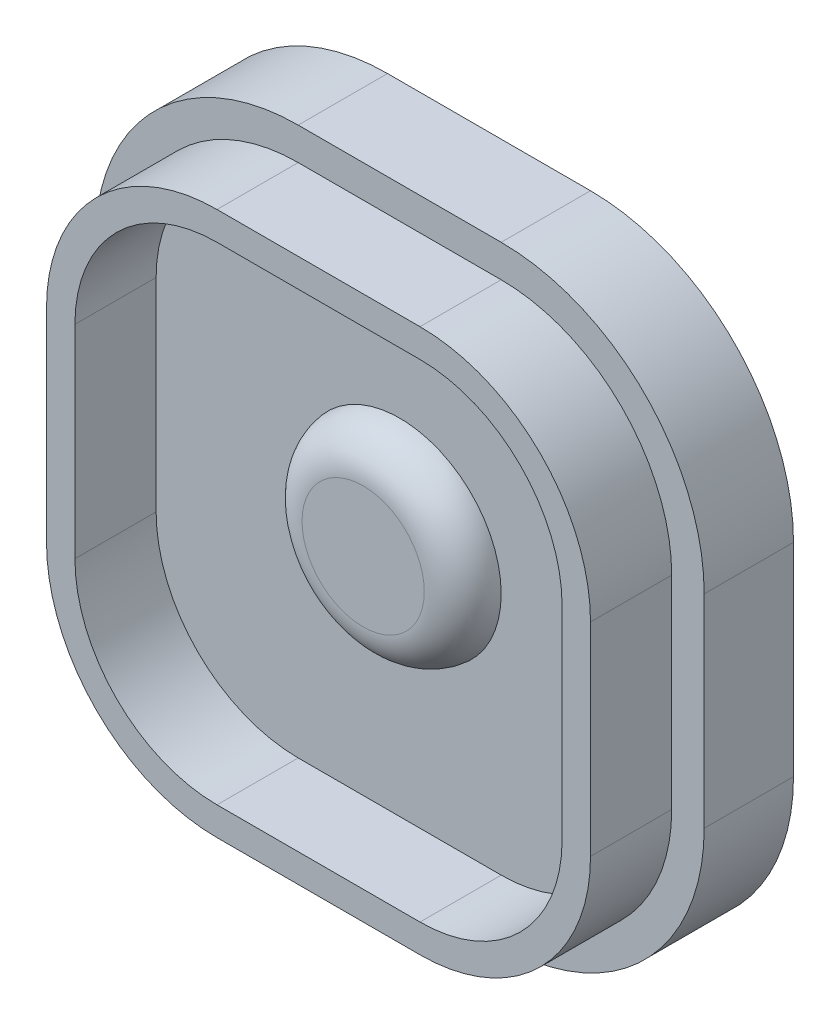
SolidWorks part; units mm, degrees
ref_plane "Front Plane" through (0, 0, 0) normal (0, 0, 1) x (1, 0, 0)
ref_plane "Top Plane" through (0, 0, 0) normal (0, 1, 0) x (1, 0, 0)
ref_plane "Right Plane" through (0, 0, 0) normal (1, 0, 0) x (0, 0, -1)
sketch "Sketch1" plane through (0, 0, 0) normal (0, 0, 1) x (1, 0, 0)
  line L2 (-1.778, 2.1553) -> (-1.778, -2.1553)
  line L4 (1.778, 2.1553) -> (1.778, -2.1553)
  arc A0 (-1.778, -2.1553) -> (1.778, -2.1553) centre (0, 0) ccw
  arc A1 (1.778, 2.1553) -> (-1.778, 2.1553) centre (0, 0) ccw
  circle A2 centre (0, 0) radius 6.35
  dimension "D1" = 5.588
  dimension "D4" = 12.7
  dimension "D2" = 3.556
  dimension "D3" = 4.3105
extrude "Boss-Extrude1" add sketch "Sketch1" along normal blind 6.096
sketch "Sketch2" plane through (0, 0, 0) normal (1, 0, 0) x (0, 0, -1)
  line L0 (-1.27, 23.622) -> (-1.27, -23.622)
  line L1 (0, -6.35) -> (0, 6.35) construction
  point P2 (-1.27, 0)
  dimension "D1" = 47.244
  dimension "D2" = 1.27
surface "Surface-Extrude1" sketch "Sketch2" parameters "D1"=6.096
ref_plane "Plane1" through (0, 0, 3.81) normal (0, 0, 1) x (1, 0, 0)
sketch "Sketch3" plane through (0, 0, 3.81) normal (0, 0, 1) x (1, 0, 0)
  line L1 (-6.35, 19.05) -> (6.35, 19.05)
  line L2 (-19.05, 6.35) -> (-19.05, -6.35)
  line L3 (-6.35, -19.05) -> (6.35, -19.05)
  line L4 (19.05, 6.35) -> (19.05, -6.35)
  line L5 (-19.05, 19.05) -> (19.05, -19.05) construction
  line L6 (-19.05, -19.05) -> (19.05, 19.05) construction
  arc A1 (6.35, 19.05) -> (19.05, 6.35) centre (6.35, 6.35) cw
  arc A2 (6.35, -19.05) -> (19.05, -6.35) centre (6.35, -6.35) ccw
  arc A3 (-19.05, -6.35) -> (-6.35, -19.05) centre (-6.35, -6.35) ccw
  arc A4 (-6.35, 19.05) -> (-19.05, 6.35) centre (-6.35, 6.35) ccw
  point P0 (0, 0)
  dimension "D1" = 38.1
  dimension "D3" = 12.7
  dimension "D2" = 38.1
extrude "Boss-Extrude2" add sketch "Sketch3" along normal blind 1.778
sketch "Sketch4" plane through (0, 0, 5.588) normal (0, 0, 1) x (1, 0, 0)
  line L0 (-1.778, 2.1553) -> (-1.778, -2.1553)
  line L1 (1.778, 2.1553) -> (1.778, -2.1553)
  arc A0 (-1.778, -2.1553) -> (1.778, -2.1553) centre (0, 0) ccw
  arc A1 (1.778, 2.1553) -> (-1.778, 2.1553) centre (0, 0) ccw
extrude "Cut-Extrude1" cut sketch "Sketch4" against normal blind 1.778
sketch "Sketch5" plane through (0, 0, 6.096) normal (0, 0, 1) x (1, 0, 0)
  circle A0 centre (0, 0) radius 6.35
extrude "Boss-Extrude3" add sketch "Sketch5" along normal blind 1.778
fillet "Fillet2" radius 2.54 1 edges at (6.35, 0, 7.874)
sketch "Sketch6" plane through (0, 0, 3.81) normal (0, 0, -1) x (-1, 0, 0)
  line L0 (6.35, -19.05) -> (-6.35, -19.05) construction
  line L1 (-6.35, 19.05) -> (6.35, 19.05)
  line L2 (-19.05, 6.35) -> (-19.05, -6.35)
  line L3 (-6.35, -19.05) -> (6.35, -19.05)
  line L4 (19.05, 6.35) -> (19.05, -6.35)
  line L5 (-6.35, 19.05) -> (6.35, 19.05) construction
  line L6 (-17.272, 6.35) -> (-17.272, -6.35)
  line L7 (-6.35, -17.272) -> (6.35, -17.272)
  line L8 (17.272, 6.35) -> (17.272, -6.35)
  line L9 (-6.35, 17.272) -> (6.35, 17.272)
  arc A0 (-19.05, -6.35) -> (-6.35, -19.05) centre (-6.35, -6.35) ccw
  arc A1 (6.35, -19.05) -> (19.05, -6.35) centre (6.35, -6.35) ccw
  arc A2 (6.35, 19.05) -> (19.05, 6.35) centre (6.35, 6.35) cw
  arc A3 (-6.35, 19.05) -> (-19.05, 6.35) centre (-6.35, 6.35) ccw
  arc A4 (-17.272, -6.35) -> (-6.35, -17.272) centre (-6.35, -6.35) ccw
  arc A5 (6.35, -17.272) -> (17.272, -6.35) centre (6.35, -6.35) ccw
  arc A6 (6.35, 17.272) -> (17.272, 6.35) centre (6.35, 6.35) cw
  arc A7 (-6.35, 17.272) -> (-17.272, 6.35) centre (-6.35, 6.35) ccw
  point P14 (19.05, 19.05)
  point P17 (-19.05, 19.05)
  dimension "D2" = 12.7
  dimension "D1" = 38.1
  dimension "D3" = 1.778
extrude "Boss-Extrude5" add sketch "Sketch6" along normal blind 3.81
sketch "Sketch7" plane through (0, 0, 5.588) normal (0, 0, 1) x (1, 0, 0)
  line L0 (-17.018, 6.35) -> (-17.018, -6.35)
  line L1 (-6.35, 19.05) -> (6.35, 19.05)
  line L2 (-19.05, 6.35) -> (-19.05, -6.35)
  line L3 (-6.35, -19.05) -> (6.35, -19.05)
  line L4 (19.05, 6.35) -> (19.05, -6.35)
  line L5 (-19.05, 19.05) -> (19.05, -19.05) construction
  line L6 (-19.05, -19.05) -> (19.05, 19.05) construction
  line L7 (-6.35, -17.018) -> (6.35, -17.018)
  line L8 (17.018, 6.35) -> (17.018, -6.35)
  line L9 (-6.35, 17.018) -> (6.35, 17.018)
  line L10 (-15.24, 6.35) -> (-15.24, -6.35)
  line L11 (-6.35, -15.24) -> (6.35, -15.24)
  line L12 (15.24, 6.35) -> (15.24, -6.35)
  line L13 (-6.35, 15.24) -> (6.35, 15.24)
  arc A0 (-19.05, -6.35) -> (-6.35, -19.05) centre (-6.35, -6.35) ccw
  arc A1 (6.35, -19.05) -> (19.05, -6.35) centre (6.35, -6.35) ccw
  arc A2 (6.35, 19.05) -> (19.05, 6.35) centre (6.35, 6.35) cw
  arc A3 (-6.35, 19.05) -> (-19.05, 6.35) centre (-6.35, 6.35) ccw
  arc A4 (-17.018, -6.35) -> (-6.35, -17.018) centre (-6.35, -6.35) ccw
  arc A5 (6.35, -17.018) -> (17.018, -6.35) centre (6.35, -6.35) ccw
  arc A6 (6.35, 17.018) -> (17.018, 6.35) centre (6.35, 6.35) cw
  arc A7 (-6.35, 17.018) -> (-17.018, 6.35) centre (-6.35, 6.35) ccw
  arc A8 (-15.24, -6.35) -> (-6.35, -15.24) centre (-6.35, -6.35) ccw
  arc A9 (6.35, -15.24) -> (15.24, -6.35) centre (6.35, -6.35) ccw
  arc A10 (6.35, 15.24) -> (15.24, 6.35) centre (6.35, 6.35) cw
  arc A11 (-6.35, 15.24) -> (-15.24, 6.35) centre (-6.35, 6.35) ccw
  point P0 (0, 0)
  dimension "D3" = 12.7
  dimension "D1" = 38.1
  dimension "D2" = 38.1
  dimension "D4" = 2.032
  dimension "D5" = 1.778
extrude "Boss-Extrude6" add sketch "Sketch7" along normal blind 5.08 contours L9 A7 L0 A4 L7 A5 L8 A6 A11 L13 A10 L12 A9 L11 A8 L10
